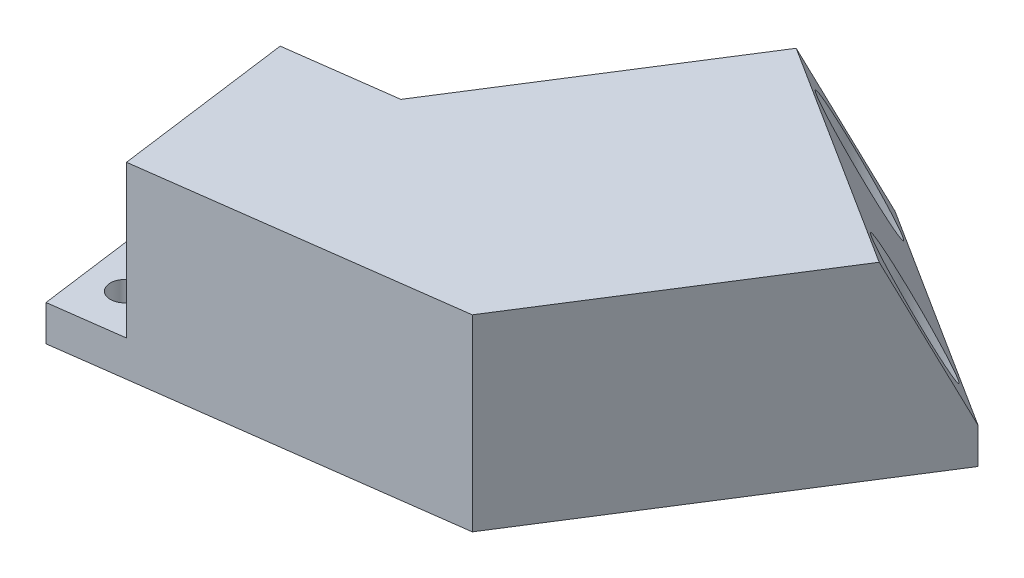
SolidWorks part; units mm, degrees
ref_plane "Спереди" through (0, 0, 0) normal (0, 0, 1) x (1, 0, 0)
ref_plane "Сверху" through (0, 0, 0) normal (0, 1, 0) x (1, 0, 0)
ref_plane "Справа" through (0, 0, 0) normal (1, 0, 0) x (0, 0, -1)
sketch "Sketch1" plane through (0, 0, 0) normal (0, 1, 0) x (1, 0, 0)
  line L0 (0, 0) -> (-19.8234, -2.6518)
  line L1 (-19.8234, -2.6518) -> (-17.1716, -22.4752)
  line L2 (-17.1716, -22.4752) -> (24.8344, -16.856)
  line L3 (24.8344, -16.856) -> (46.7569, 17.7141)
  line L4 (46.7569, 17.7141) -> (21.4217, 33.7803)
  line L5 (21.4217, 33.7803) -> (0, 0)
  line L6 (0, 0) -> (2.6518, -19.8234) construction
  dimension "D1" = 130
  dimension "D2" = 20
  dimension "D3" = 20
  dimension "D4" = 30
  dimension "D5" = 90
  dimension "D6" = 40
extrude "Boss-Extrude1" add sketch "Sketch1" along normal blind 21
sketch "Sketch2" plane through (0, 21, 0) normal (0, 1, 0) x (1, 0, 0)
  line L0 (21.4217, 33.7803) -> (17.1373, 27.0243)
  line L1 (21.4217, 33.7803) -> (0, 0) construction
  line L2 (17.1373, 27.0243) -> (42.4726, 10.958)
  line L3 (24.8344, -16.856) -> (46.7569, 17.7141) construction
  line L4 (42.4726, 10.958) -> (46.7569, 17.7141)
  line L5 (46.7569, 17.7141) -> (21.4217, 33.7803)
  line L6 (-19.8234, -2.6518) -> (-17.1716, -22.4752)
  line L7 (-17.1716, -22.4752) -> (-9.2422, -21.4145)
  line L8 (-17.1716, -22.4752) -> (24.8344, -16.856) construction
  line L9 (-9.2422, -21.4145) -> (-11.8941, -1.5911)
  line L10 (0, 0) -> (-19.8234, -2.6518) construction
  line L11 (-11.8941, -1.5911) -> (-19.8234, -2.6518)
  dimension "D1" = 8
extrude "Cut-Extrude1" cut sketch "Sketch2" against normal offset from surface (17 mm away) 4 up to face at (9.3363, 0, -1.5852)
sketch "Sketch3" plane through (0, 21, 0) normal (0, 1, 0) x (1, 0, 0)
  line L0 (18.0642, 22.8841) -> (1.7843, -2.788)
  line L1 (1.7843, -2.788) -> (-8.5228, -4.1668)
  line L2 (-8.5228, -4.1668) -> (-6.6665, -18.0432)
  line L3 (-6.6665, -18.0432) -> (23.0501, -14.068)
  line L4 (23.0501, -14.068) -> (38.3324, 10.0311)
  line L5 (38.3324, 10.0311) -> (18.0642, 22.8841)
  line L6 (18.0642, 22.8841) -> (17.864, 23.073)
  line L7 (17.1373, 27.0243) -> (0, 0) construction
  line L9 (0, 0) -> (-11.8941, -1.5911) construction
  line L10 (-9.2422, -21.4145) -> (-11.8941, -1.5911) construction
  line L11 (-9.2422, -21.4145) -> (24.8344, -16.856) construction
  line L12 (24.8344, -16.856) -> (42.4726, 10.958) construction
  line L13 (17.1373, 27.0243) -> (42.4726, 10.958) construction
  dimension "D1" = 3
  dimension "D2" = 3
  dimension "D3" = 3
  dimension "D4" = 3
  dimension "D5" = 3
  dimension "D6" = 3
extrude "Cut-Extrude2" cut sketch "Sketch3" against normal through all from offset 3 contours L4 L5 L0 L1 L2 L3 region at (15.3861, 21, 0.1653) offset against normal yes
sketch "Sketch4" plane through (2.5335, 0, 1.6066) normal (0.8445, 0, 0.5355) x (0.5355, 0, -0.8445)
  line L0 (13.8005, 0) -> (13.8005, 18) construction
  line L1 (29, 0) -> (-1.3989, 0) construction
  line L2 (29, 18) -> (-1.3989, 18) construction
  line L4 (3.3005, 1) -> (24.3005, 1) construction
  line L5 (3.3005, 1) -> (3.3005, 17) construction
  line L6 (3.3005, 17) -> (24.3005, 17) construction
  line L7 (24.3005, 1) -> (24.3005, 17) construction
  line L8 (3.3005, 1) -> (24.3005, 17) construction
  line L9 (3.3005, 17) -> (24.3005, 1) construction
  circle A0 centre (13.8005, 9) radius 4.5
  dimension "D1" = 9
  dimension "D2" = 16
  dimension "D3" = 21
extrude "Cut-Extrude3" cut sketch "Sketch4" against normal through all
sketch "Sketch5" plane through (0, 4, 0) normal (0, 1, 0) x (1, 0, 0)
  line L0 (19.2795, 30.4023) -> (44.6148, 14.3361) construction
  line L1 (21.4217, 33.7803) -> (17.1373, 27.0243) construction
  line L2 (42.4726, 10.958) -> (46.7569, 17.7141) construction
  line L3 (-15.8587, -2.1215) -> (-13.2069, -21.9449) construction
  line L4 (-11.8941, -1.5911) -> (-19.8234, -2.6518) construction
  line L5 (-17.1716, -22.4752) -> (-9.2422, -21.4145) construction
  circle A0 centre (23.5021, 27.7246) radius 1.6
  circle A1 centre (40.3922, 17.0138) radius 1.6
  circle A2 centre (-15.1958, -7.0773) radius 1.6
  circle A3 centre (-13.8699, -16.989) radius 1.6
  point P20 (-14.5328, -12.0332)
  point P21 (31.9471, 22.3692)
  dimension "D1" = 3.2
  dimension "D2" = 10
  dimension "D3" = 5
  dimension "D4" = 20
  dimension "D5" = 10
extrude "Cut-Extrude4" cut sketch "Sketch5" against normal through all
sketch "Sketch6" plane through (0, 0, 0) normal (-0.8445, 0, -0.5355) x (-0.5355, 0, 0.8445)
  line L0 (-24, 0) -> (-24, 21) construction
  line L1 (-40, 0) -> (0, 0) construction
  line L2 (-32, 21) -> (0, 21) construction
  line L3 (-32, 4) -> (-32, 21) construction
  text T0 "<b>    ALT</b>" font "Arial" height 3
  dimension "D1" = 8
extrude "Cut-Extrude5" cut sketch "Sketch6" against normal blind 0.5
sketch "Sketch8" plane through (0, 0, 0) normal (-0.8445, 0, -0.5355) x (-0.5355, 0, 0.8445)
  line L0 (-40, 4) -> (-32, 21)
  line L1 (-32, 21) -> (-32, 4)
  line L2 (-32, 4) -> (-40, 4)
extrude "Boss-Extrude2" add sketch "Sketch8" against normal up to surface (30 mm away) up to face at (38.0213, 8.3333, -3.9387)
sketch "Sketch10" plane through (0, 0, 0) normal (0, -1, 0) x (1, 0, 0)
  circle A0 centre (23.5021, -27.7246) radius 1.6
  circle A1 centre (40.3922, -17.0138) radius 1.6
  circle A2 centre (-15.1958, 7.0773) radius 1.6
  circle A3 centre (-13.8699, 16.989) radius 1.6
  circle A4 centre (40.3922, -17.0138) radius 1.6 construction
extrude "Cut-Extrude6" cut sketch "Sketch10" against normal through all
sketch "Sketch11" plane through (0, 0, 0) normal (0, -1, 0) x (1, 0, 0)
  circle A0 centre (-15.1958, 7.0773) radius 3.5
  circle A1 centre (-13.8699, 16.989) radius 3.5
  circle A2 centre (40.3922, -17.0138) radius 3.5
  circle A3 centre (23.5021, -27.7246) radius 3.5
  dimension "D1" = 7
extrude "Cut-Extrude7" cut sketch "Sketch11" against normal through all from offset 4 offset against normal yes
sketch "Sketch12" plane through (-8.9205, 0, 1.1933) normal (0.9912, 0, -0.1326) x (-0.1326, 0, -0.9912)
  line L0 (-10, 0) -> (-10, 18) construction
  line L1 (-3, 0) -> (-17, 0) construction
  line L2 (-3, 18) -> (-17, 18) construction
  circle A0 centre (-10, 11) radius 3
  dimension "D1" = 6
  dimension "D2" = 11
extrude "Cut-Extrude8" cut sketch "Sketch12" against normal through all
sketch "Sketch13" plane through (0, 0, 0) normal (-0.1326, 0, -0.9912) x (-0.9912, 0, 0.1326)
  line L0 (7, 0) -> (7, 21) construction
  line L1 (0, 0) -> (20, 0) construction
  line L2 (0, 21) -> (12, 21) construction
  line L3 (12, 4) -> (12, 21) construction
  text T0 "<b>     R / B</b>" font "Arial" height 3
  dimension "D1" = 5
extrude "Cut-Extrude9" cut sketch "Sketch13" against normal blind 0.5
